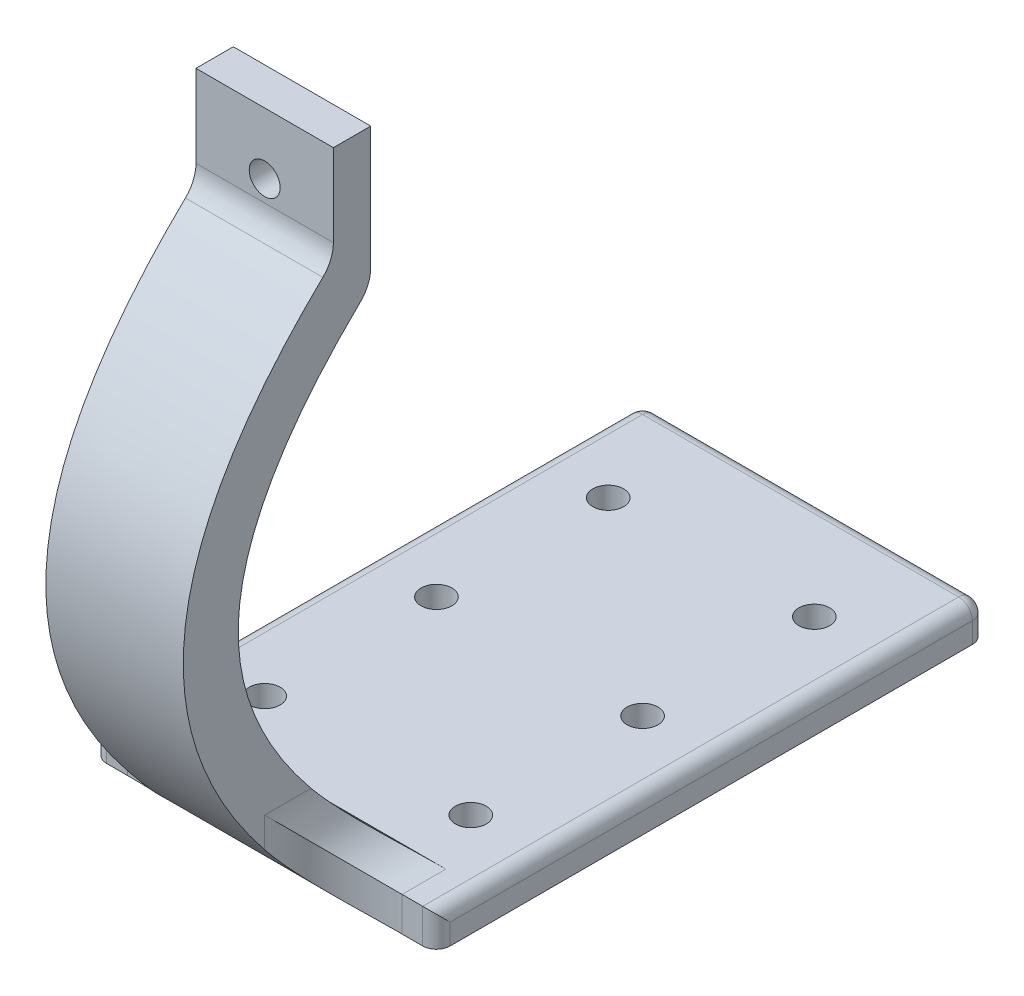
SolidWorks part; units mm, degrees
ref_plane "Front Plane" through (0, 0, 0) normal (0, 0, 1) x (1, 0, 0)
ref_plane "Top Plane" through (0, 0, 0) normal (0, 1, 0) x (1, 0, 0)
ref_plane "Right Plane" through (0, 0, 0) normal (1, 0, 0) x (0, 0, -1)
sketch "Sketch1" plane through (0, 0, 0) normal (0, 1, 0) x (1, 0, 0)
  line L1 (-25, 40) -> (25, 40)
  line L2 (-25, 40) -> (-25, -40)
  line L3 (-25, -40) -> (25, -40)
  line L4 (25, 40) -> (25, -40)
  line L5 (-25, 40) -> (25, -40) construction
  line L6 (-25, -40) -> (25, 40) construction
  point P0 (0, 0)
  dimension "D1" = 50
  dimension "D2" = 80
extrude "Boss-Extrude1" add sketch "Sketch1" along normal blind 5
sketch "Sketch2" plane through (0, 5, 0) normal (0, 1, 0) x (1, 0, 0)
  line L0 (-15, 40) -> (-15, -40) construction
  line L1 (25, 40) -> (-25, 40) construction
  line L2 (-25, -40) -> (25, -40) construction
  line L3 (0, 40) -> (0, -40) construction
  circle A0 centre (-15, 0) radius 2.25
  circle A1 centre (-15, 25) radius 2.25
  circle A2 centre (-15, -25) radius 2.25
  circle A3 centre (15, -25) radius 2.25
  circle A4 centre (15, 0) radius 2.25
  circle A5 centre (15, 25) radius 2.25
  dimension "D1" = 4.5
  dimension "D2" = 4.5
  dimension "D3" = 4.5
  dimension "D4" = 25
  dimension "D5" = 25
  dimension "D6" = 15
extrude "Cut-Extrude1" cut sketch "Sketch2" against normal through all
sketch "Sketch4" plane through (0, 0, 0) normal (1, 0, 0) x (0, 0, -1)
  line L0 (-40, 0) -> (-40, 80) construction
  line L1 (-61.8503, 50.4903) -> (-61.8503, 29.2693) construction
  line L2 (-34.565, 5.8704) -> (-33.6249, 5)
  line L3 (-40, 5) -> (40, 5) construction
  line L4 (-40, 0) -> (-33.6249, 5)
  line L5 (-34.5639, 74.1307) -> (-34.5639, 80)
  line L7 (-34.5639, 74.1307) -> (-34.5639, 94.1307)
  line L8 (-34.5639, 94.1307) -> (-40, 94.1307)
  line L9 (-40, 94.1307) -> (-40, 80)
  spline S0 degree 3 poles (-40, 0) (-69.4701, 27.2842) (-68.7954, 53.3297) (-40, 80) knots 0 0 0 0 1 1 1 1
  spline S1 degree 1 poles (-34.565, 5.8704) (-34.5639, 74.1307) knots 0 0 1 1 construction
  spline S2 degree 3 poles (-34.565, 5.8704) (-34.9911, 6.2648) (-35.8438, 7.0665) (-37.4711, 8.6458) (-39.3962, 10.6089) (-41.5214, 12.9344) (-44.1142, 15.9961) (-46.9065, 19.7435) (-49.5605, 24.0989) (-51.5494, 28.304) (-53.3675, 33.719) (-54.1987, 40.1809) (-53.2849, 46.6351) (-51.4126, 52.0249) (-49.3955, 56.1978) (-46.7327, 60.5055) (-43.9557, 64.199) (-41.3922, 67.209) (-39.2985, 69.4916) (-37.4083, 71.4152) (-35.8141, 72.9612) (-34.9805, 73.7449) (-34.5639, 74.1307) knots 0 0 0 0 0.015625 0.03125 0.0625 0.09375 0.125 0.1875 0.25 0.3125 0.375 0.5 0.625 0.6875 0.75 0.8125 0.875 0.90625 0.9375 0.96875 0.984375 1 1 1 1
  dimension "D1" = 80
  dimension "D3" = 20
  dimension "D2" = 8
extrude "Boss-Extrude2" add sketch "Sketch4" along normal mid plane 20 contours L2 S2 L5 L7 L8 L9 S0 L4 region at (0, 4.7141, 34.7626)
fillet "Fillet1" radius 10 4 edges at (-10, 5, 36.8125) (-10, 2.5, 40) (10, 2.5, 40) (10, 5, 36.8125)
fillet "Fillet2" radius 5 2 edges at (0, 80, 40) (0, 74.1307, 34.5639)
sketch "Sketch5" plane through (0, 0, 34.5639) normal (0, 0, -1) x (-1, 0, 0)
  line L0 (0, 94.1307) -> (0, 76.2869) construction
  line L1 (-10, 94.1307) -> (10, 94.1307) construction
  line L2 (-10, 76.2869) -> (10, 76.2869) construction
  circle A0 centre (0, 85.2088) radius 2.25
  dimension "D1" = 4.5
extrude "Cut-Extrude2" cut sketch "Sketch5" against normal through all
fillet "Fillet3" radius 2 7 edges at (-25, 2.5, 40) (-25, 2.5, -40) (25, 2.5, -40) (25, 2.5, 40) (-25, 5, 0) (0, 5, -40) (25, 5, 0)
